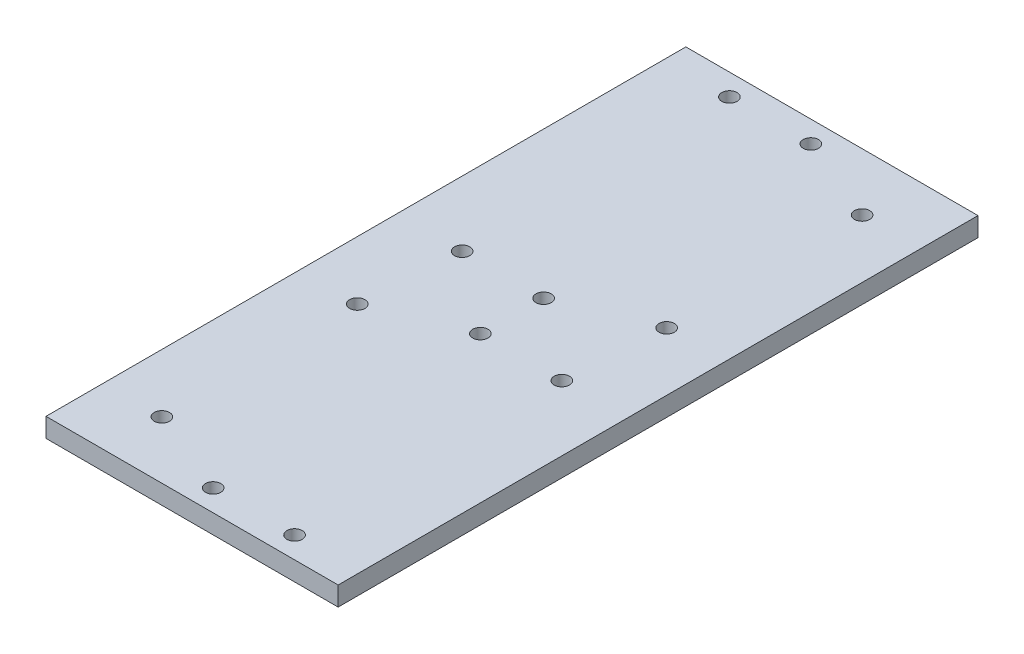
SolidWorks part; units mm, degrees
ref_plane "前视基准面" through (0, 0, 0) normal (0, 0, 1) x (1, 0, 0)
ref_plane "上视基准面" through (0, 0, 0) normal (0, 1, 0) x (1, 0, 0)
ref_plane "右视基准面" through (0, 0, 0) normal (1, 0, 0) x (0, 0, -1)
other "Configuration Table"
sketch "草图1" plane through (0, 0, 0) normal (0, 1, 0) x (1, 0, 0)
  line L1 (0, 0) -> (30.5, 0)
  line L2 (0, 0) -> (0, -66.8)
  line L3 (0, -66.8) -> (30.5, -66.8)
  line L4 (30.5, 0) -> (30.5, -66.8)
  circle A4 centre (6.8, -2.25) radius 0.8
  circle A5 centre (15.3, -2.25) radius 0.8
  circle A6 centre (15.2, -64.55) radius 0.8
  circle A7 centre (23.7, -64.55) radius 0.8
  circle A10 centre (6.8, -2.25) radius 1.3
  circle A11 centre (15.3, -2.25) radius 1.3
  circle A12 centre (15.2, -64.55) radius 1.3
  circle A13 centre (23.7, -64.55) radius 1.3
  circle A22 centre (24.4, -6) radius 1.3
  circle A23 centre (24.4, -26.4) radius 1.3
  circle A24 centre (6.8, -30.15) radius 1.3
  circle A25 centre (6.1, -60.8) radius 1.3
  circle A26 centre (23.7, -36.65) radius 1.3
  circle A27 centre (6.1, -40.4) radius 1.3
  circle A28 centre (15.2, -36.65) radius 1.3
  circle A29 centre (15.3, -30.15) radius 1.3
  circle A30 centre (24.4, -6) radius 0.8
  circle A31 centre (24.4, -26.4) radius 0.8
  circle A32 centre (6.1, -60.8) radius 0.8
  circle A33 centre (6.8, -30.15) radius 0.8
  circle A34 centre (6.1, -40.4) radius 0.8
  circle A35 centre (23.7, -36.65) radius 0.8
  circle A36 centre (15.3, -30.15) radius 0.8
  circle A37 centre (15.2, -36.65) radius 0.8
  dimension "D3" = 1.6
  dimension "D8" = 2.6
  dimension "D6" = 2.25
  dimension "D7" = 6.8
  dimension "D1" = 6.1
  dimension "D2" = 30.5
  dimension "D4" = 20.4
  dimension "D5" = 6
  dimension "D9" = 8.5
  dimension "D10" = 27.9
  dimension "D11" = 6.1
  dimension "32.4" = 66.8
  dimension "D12" = 6
  dimension "D13" = 20.4
  dimension "D14" = 2.25
  dimension "D15" = 6.8
  dimension "D16" = 8.5
  dimension "D17" = 27.9
extrude "凸台-拉伸1" add sketch "草图1" along normal blind 2 contours L1 | L2 L3 L4 L1 | A7 | A6 | A4 | A5 | A32 | A34 | A37 | A35 | A36 | A33 | A31 | A30
